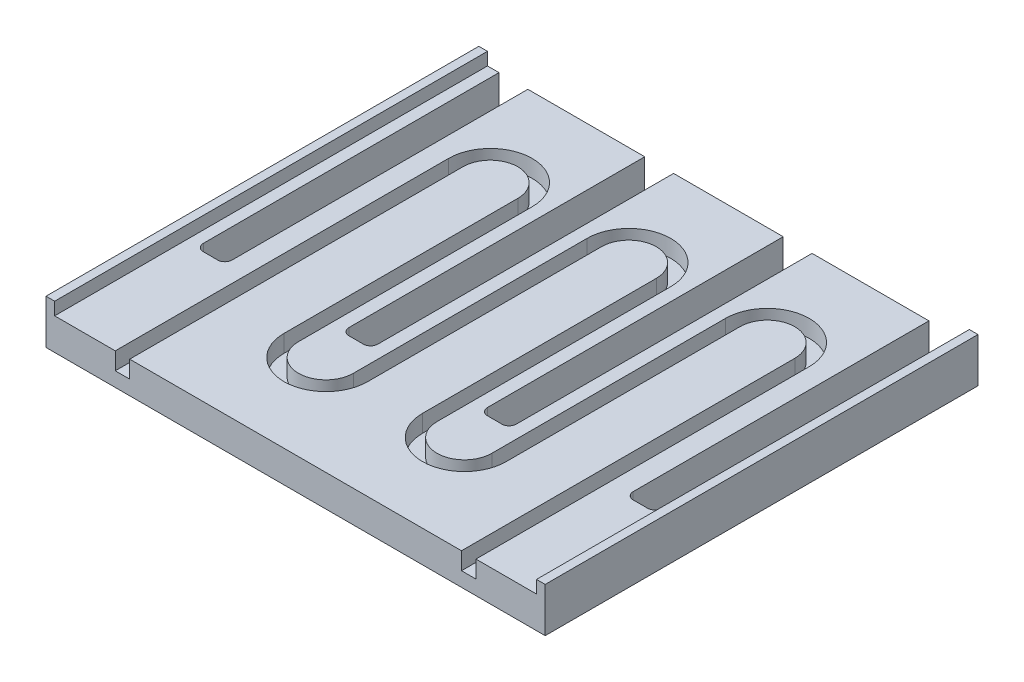
SolidWorks part; units mm, degrees
ref_plane "Спереди" through (0, 0, 0) normal (0, 0, 1) x (1, 0, 0)
ref_plane "Сверху" through (0, 0, 0) normal (0, 1, 0) x (1, 0, 0)
ref_plane "Справа" through (0, 0, 0) normal (1, 0, 0) x (0, 0, -1)
sketch "Подложка трубки" plane through (0, 0, 0) normal (0, 1, 0) x (1, 0, 0)
  line L0 (5.3073, 0.8937) -> (101.8191, 0.8937) construction
  line L1 (12, 0) -> (12, 50)
  line L2 (0, 0) -> (2.5, 0)
  line L3 (0, 0) -> (0, 50)
  line L4 (0, 50) -> (2.5, 50)
  line L5 (2.5, 0) -> (2.5, 50)
  line L6 (12, 0) -> (14.5, 0)
  line L7 (14.5, 0) -> (14.5, 50)
  line L8 (12, 50) -> (14.5, 50)
  line L9 (24, 0) -> (24, 50)
  line L10 (24, 0) -> (26.5, 0)
  line L11 (26.5, 0) -> (26.5, 50)
  line L12 (24, 50) -> (26.5, 50)
  line L13 (36, 0) -> (36, 50)
  line L14 (36, 0) -> (38.5, 0)
  line L15 (38.5, 0) -> (38.5, 50)
  line L16 (36, 50) -> (38.5, 50)
  line L17 (48, 0) -> (48, 50)
  line L18 (48, 0) -> (50.5, 0)
  line L19 (50.5, 0) -> (50.5, 50)
  line L20 (48, 50) -> (50.5, 50)
  line L21 (60, 0) -> (60, 50)
  line L22 (60, 0) -> (62.5, 0)
  line L23 (62.5, 0) -> (62.5, 50)
  line L24 (60, 50) -> (62.5, 50)
  line L25 (62.9198, 62.5) -> (-29.5124, 62.5) construction
  line L26 (0, 50) -> (14.5, 50)
  line L27 (0, 50) -> (0, 52.5)
  line L28 (0, 52.5) -> (14.5, 52.5)
  line L29 (14.5, 50) -> (14.5, 52.5)
  line L30 (24, 50) -> (38.5, 50)
  line L31 (24, 50) -> (24, 52.5)
  line L32 (24, 52.5) -> (38.5, 52.5)
  line L33 (38.5, 50) -> (38.5, 52.5)
  line L34 (48, 50) -> (62.5, 50)
  line L35 (48, 50) -> (48, 52.5)
  line L36 (48, 52.5) -> (62.5, 52.5)
  line L37 (62.5, 50) -> (62.5, 52.5)
  line L38 (12, 0) -> (26.5, 0)
  line L39 (12, 0) -> (12, -2.5)
  line L40 (12, -2.5) -> (26.5, -2.5)
  line L41 (26.5, 0) -> (26.5, -2.5)
  line L42 (36, 0) -> (50.5, 0)
  line L43 (36, 0) -> (36, -2.5)
  line L44 (36, -2.5) -> (50.5, -2.5)
  line L45 (50.5, 0) -> (50.5, -2.5)
  line L46 (0, 0) -> (2.5, 0)
  line L47 (0, 0) -> (0, -12.5)
  line L48 (0, -12.5) -> (2.5, -12.5)
  line L49 (2.5, 0) -> (2.5, -12.5)
  line L50 (60, 0) -> (62.5, 0)
  line L51 (60, 0) -> (60, -12.5)
  line L52 (60, -12.5) -> (62.5, -12.5)
  line L53 (62.5, 0) -> (62.5, -12.5)
  line L54 (-81.4744, -12.5) -> (67.6729, -12.5) construction
  line L55 (0, 62.7) -> (0, -70.5156) construction
  line L56 (26.25, -2.5) -> (26.25, -20) construction
  line L57 (-12, -12.5) -> (-12, 62.5)
  line L58 (74.5, -12.5) -> (74.5, 62.5) construction
  line L59 (62.5, 58.4344) -> (62.5, -75.5615) construction
  line L60 (-12, 62.5) -> (74.5, 62.5)
  line L61 (-12, 62.5) -> (-12, -12.5)
  line L62 (-12, -12.5) -> (74.5, -12.5)
  line L63 (74.5, 62.5) -> (74.5, -12.5)
  point P25 (0, -12.5)
  point P53 (74.5, 0.8937)
  point P55 (-12, 0.8937)
  point P60 (62.5, -12.5)
  point P64 (62.5, -12.5)
  dimension "D1" = 50
  dimension "D2" = 2.5
  dimension "D4" = 12
  dimension "D5" = 2.5
  dimension "D11" = 2.5
  dimension "D14" = 2.5
  dimension "D13" = 10
  dimension "D6" = 12
  dimension "D8" = 12
  dimension "D7" = 86.5
  dimension "D9" = 75
  dimension "D3" = 6
extrude "Бобышка-Вытянуть4" add sketch "Подложка трубки" along normal blind 5.5 contours L63 L60 L57 L62 L47 L3 L27 L28 L29 L7 L38 L9 L31 L32 L33 L15 L42 L17 L35 L36 L37 L23 L53 | L49 L62 L51 L21 L34 L19 L45 L44 L43 L13 L30 L11 L41 L40 L39 L1 L26 L5 region at (31.25, 0, -15.0747) region at (15.6449, 0, -25)
extrude "Бобышка-Вытянуть6" add sketch "Подложка трубки<9>" along normal blind 2.5 contours L49 L2 L47 L48 | L2 L5 L4 L3 | L41 L10 L38 L6 L39 L40 | L8 L1 L6 L7 | L12 L9 L10 L11 | L8 L29 L28 L27 L4 L26 | L16 L33 L32 L31 L12 L30 | L16 L13 L14 L15 | L45 L18 L42 L14 L43 L44 | L20 L17 L18 L19 | L24 L37 L36 L35 L20 L34 | L24 L21 L22 L23 | L51 L52 L53 L50 region at (13.25, 0, -25) region at (19.25, 0, 1.25) region at (7.25, 0, -51.25) region at (1.25, 0, -25) region at (25.25, 0, -25) region at (1.25, 0, 6.25) region at (31.25, 0, -51.25) region at (37.25, 0, -25) region at (61.25, 0, -25) region at (43.25, 0, 1.25) region at (55.25, 0, -51.25) region at (49.25, 0, -25)
sketch "Подложка трубки<9>" plane through (0, 0, 0) normal (0, 1, 0) x (1, 0, 0) same geometry as "Подложка трубки"
sketch "DS18B20" plane through (0, 5.5, 0) normal (0, 1, 0) x (1, 0, 0)
  line L0 (-12, 5) -> (74.5, 5)
  line L1 (-12, -12.5) -> (-12, 62.5) construction
  line L2 (74.5, 62.5) -> (74.5, -12.5) construction
  line L3 (14.5, 0) -> (24, 0) construction
  line L4 (-12, 16.3698) -> (0, 20)
  line L5 (0, 52.5) -> (0, -12.5) construction
  line L6 (14.5, 20) -> (24, 20)
  line L7 (14.5, 0) -> (14.5, 52.5) construction
  line L8 (24, 0) -> (24, 52.5) construction
  line L9 (38.5, 20) -> (48, 20)
  line L10 (38.5, 0) -> (38.5, 52.5) construction
  line L11 (48, 0) -> (48, 52.5) construction
  line L12 (62.5, 20) -> (74.5, 20)
  line L13 (62.5, -12.5) -> (62.5, 52.5) construction
  line L14 (62.5, -12.5) -> (62.5, 52.5) construction
  line L15 (-12, 62.5) -> (74.5, 62.5) construction
  line L16 (66, 62.5) -> (71, 62.5)
  line L17 (66, 62.5) -> (66, 10)
  line L18 (66, 10) -> (71, 10)
  line L19 (71, 62.5) -> (71, 10)
  line L20 (14.5, 0) -> (24, 0) construction
  line L21 (-8.5, 62.5) -> (-3.5, 62.5)
  line L22 (-8.5, 62.5) -> (-8.5, 10)
  line L23 (-8.5, 10) -> (-3.5, 10)
  line L24 (-3.5, 62.5) -> (-3.5, 10)
  line L25 (16.75, 62.5) -> (21.75, 62.5)
  line L26 (16.75, 62.5) -> (16.75, 10)
  line L27 (16.75, 10) -> (21.75, 10)
  line L28 (21.75, 62.5) -> (21.75, 10)
  line L30 (40.75, 62.5) -> (45.75, 62.5)
  line L31 (40.75, 62.5) -> (40.75, 10)
  line L32 (40.75, 10) -> (45.75, 10)
  line L33 (45.75, 62.5) -> (45.75, 10)
  line M3 (74.5, 62.5) -> (-12, 62.5)
  dimension "D4" = 12
  dimension "D1" = 5
  dimension "D6" = 5
  dimension "D7" = 9.5
  dimension "D8" = 2.25
  dimension "D2" = 2.25
  dimension "D3" = 3.5
  dimension "D5" = 3.5
  dimension "D9" = 10
extrude "Вырез-Вытянуть1" cut sketch "DS18B20" against normal blind 5 contours L24 L22 L4 M3 | L24 L4 L22 L23 | L28 L26 L6 M3 | L28 L6 L26 L27 | L33 L31 L9 M3 | L33 L9 L31 L32 | L19 L17 L12 M3 | L19 L12 L17 L18 region at (-6.0142, 5.5, -40.3403) region at (68.5, 5.5, -41.25) region at (43.25, 5.5, -41.25) region at (19.25, 5.5, -41.25) region at (-5.923, 5.5, -14.1041) region at (19.25, 5.5, -15) region at (43.25, 5.5, -15) region at (68.5, 5.5, -15)
sketch "Эскиз7" plane through (0, 5.5, 0) normal (0, 1, 0) x (1, 0, 0)
  line L0 (-12, -12.5) -> (0, -12.5) construction
  line L1 (-12, 62.5) -> (-10.5, 62.5)
  line L2 (-12, 62.5) -> (-12, -12.5)
  line L3 (-12, -12.5) -> (-10.5, -12.5)
  line L4 (-10.5, 62.5) -> (-10.5, -12.5)
  line L5 (62.5, -12.5) -> (74.5, -12.5) construction
  line L6 (74.5, 62.5) -> (73, 62.5)
  line L7 (74.5, 62.5) -> (74.5, -12.5)
  line L8 (74.5, -12.5) -> (73, -12.5)
  line L9 (73, 62.5) -> (73, -12.5)
  dimension "D1" = 1.5
extrude "Бобышка-Вытянуть8" add sketch "Эскиз7" along normal blind 2.2
fillet "Скругление1" 2 edges at (60, 4, -50) (50.5, 4, -50) type full round first side face at (60, 4, -18.75) second side face at (50.5, 4, -23.75) middle face at (55.25, 4, -50)
fillet "Скругление2" 2 edges at (62.5, 4, -52.5) (48, 4, -52.5) type full round first side face at (62.5, 4, -20) second side face at (48, 4, -26.25) middle face at (55.25, 4, -52.5)
fillet "Скругление3" 2 edges at (48, 4, 0) (38.5, 4, 0) type full round first side face at (48, 4, -22.625) second side face at (38.5, 4, -26.25) middle face at (43.25, 4, 0)
fillet "Скругление4" 2 edges at (50.5, 4, 2.5) (36, 4, 2.5) type full round first side face at (50.5, 4, -21.375) second side face at (36, 4, -23.75) middle face at (43.25, 4, 2.5)
fillet "Скругление5" 2 edges at (36, 4, -50) (26.5, 4, -50) type full round first side face at (36, 4, -27.375) second side face at (26.5, 4, -23.75) middle face at (31.25, 4, -50)
fillet "Скругление6" 2 edges at (38.5, 4, -52.5) (24, 4, -52.5) type full round first side face at (38.5, 4, -28.625) second side face at (24, 4, -26.25) middle face at (31.25, 4, -52.5)
fillet "Скругление7" 2 edges at (26.5, 4, 2.5) (12, 4, 2.5) type full round first side face at (26.5, 4, -21.375) second side face at (12, 4, -23.75) middle face at (19.25, 4, 2.5)
fillet "Скругление8" 2 edges at (14.5, 4, 0) (24, 4, 0) type full round first side face at (14.5, 4, -26.25) second side face at (24, 4, -22.625) middle face at (19.25, 4, 0)
fillet "Скругление9" 2 edges at (12, 4, -50) (2.5, 4, -50) type full round first side face at (12, 4, -27.375) second side face at (2.5, 4, -18.75) middle face at (7.25, 4, -50)
fillet "Скругление10" 2 edges at (14.5, 4, -52.5) (0, 4, -52.5) type full round first side face at (14.5, 4, -28.625) second side face at (0, 4, -20) middle face at (7.25, 4, -52.5)
fillet "Fillet1" radius 1.25 1 edges at (-8.5, 3, -10)
fillet "Fillet2" radius 1.25 7 edges at (-3.5, 3, -10) (16.75, 3, -10) (21.75, 3, -10) (40.75, 3, -10) (45.75, 3, -10) (71, 3, -10) (66, 3, -10)
equation "\"Tube\" = 2.5"
equation "\"D5@Подложка трубки\"=\"Tube\""
equation "\"D11@Подложка трубки\"=\"Tube\""
equation "\"D14@Подложка трубки\"=\"Tube\""
equation "\"D2@Подложка трубки\"=\"Tube\""
equation "\"Offset1\"= 12"
equation "\"D6@Подложка трубки\"=\"Offset1\""
equation "\"D8@Подложка трубки\"=\"Offset1\""
equation "\"Height\"= 3 + \"Tube\""
equation "\"D1@Бобышка-Вытянуть4\"=\"Height\""
equation "\"D1@Бобышка-Вытянуть6\"=\"Tube\""
equation "\"Pattern\" = 12"
equation "\"D4@Подложка трубки\"=\"Pattern\""
equation "\"Temp\" = 5"
equation "\"tempOffset\" = 5"
equation "\"D1@DS18B20\" = \"tempOffset\""
equation "\"D6@DS18B20\" = \"Temp\""
equation "\"D8@DS18B20\" =  ( \"D7@DS18B20\" - \"Temp\" )  / 2"
equation "\"D2@DS18B20\" =  ( \"D7@DS18B20\" - \"Temp\" )  / 2"
equation "\"D3@DS18B20\" =  ( \"D4@DS18B20\" - \"Temp\" )  / 2"
equation "\"D5@DS18B20\" =  ( \"D4@DS18B20\" - \"Temp\" )  / 2"
equation "\"D1@Вырез-Вытянуть1\"=\"Temp\""
